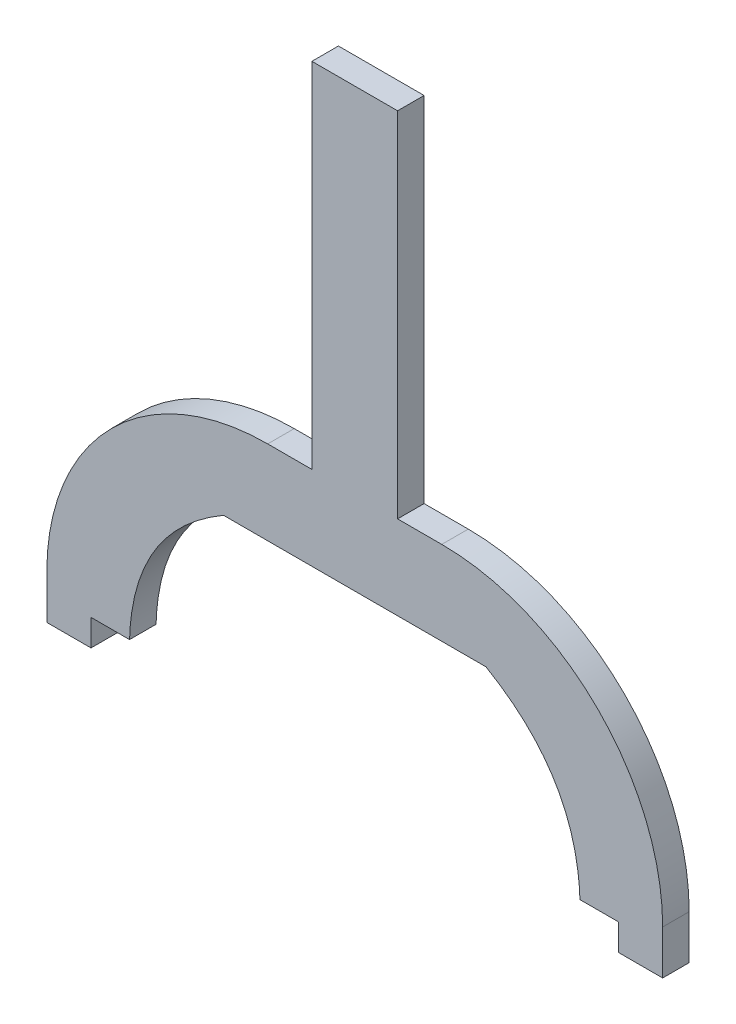
SolidWorks part; units mm, degrees
ref_plane "Front Plane" through (0, 0, 0) normal (0, 0, 1) x (1, 0, 0)
ref_plane "Top Plane" through (0, 0, 0) normal (0, 1, 0) x (1, 0, 0)
ref_plane "Right Plane" through (0, 0, 0) normal (1, 0, 0) x (0, 0, -1)
sketch "Sketch2" plane through (0, 0, 0) normal (0, 0, 1) x (1, 0, 0)
  line L40 (12.3158, -50.8) -> (88.5158, -50.8)
  line L41 (-12.3158, -50.8) -> (12.3158, -50.8) construction
  line L42 (-12.3158, -50.8) -> (-12.3158, 50.8)
  line L43 (-12.3158, 50.8) -> (12.3158, 50.8)
  line L44 (12.3158, -50.8) -> (12.3158, 50.8)
  line L45 (-12.3158, -50.8) -> (12.3158, 50.8) construction
  line L46 (-12.3158, 50.8) -> (12.3158, -50.8) construction
  line L47 (88.5158, -50.8) -> (88.5158, -127)
  line L53 (37.7158, -119.38) -> (37.7158, -74.93)
  line L54 (37.7158, -74.93) -> (-37.7158, -74.93)
  line L55 (-37.7158, -74.93) -> (-37.7158, -119.38)
  line L61 (-88.5158, -127) -> (-88.5158, -50.8)
  line L62 (-88.5158, -50.8) -> (-12.3158, -50.8)
  line L63 (37.7158, -119.38) -> (75.8158, -119.38)
  line L64 (75.8158, -119.38) -> (75.8158, -127)
  line L65 (75.8158, -127) -> (88.5158, -127)
  line L66 (-88.5158, -127) -> (-75.8158, -127)
  line L67 (-75.8158, -127) -> (-75.8158, -119.38)
  line L68 (-75.8158, -119.38) -> (-37.7158, -119.38)
  point P0 (0, 0)
  dimension "D1" = 76.2
  dimension "D2" = 44.45
  dimension "D3" = 101.6
  dimension "D4" = 7.62
  dimension "D5" = 38.1
  dimension "D6" = 12.7
  dimension "D7" = 76.2
extrude "Boss-Extrude1" add sketch "Sketch2" along normal blind 7.62
fillet "Fillet1" radius 63.5 2 edges at (88.5158, -50.8, 3.81) (-88.5158, -50.8, 3.81)
sketch "Sketch3" plane through (0, 0, 7.62) normal (0, 0, 1) x (1, 0, 0)
  line L0 (-75.8158, -119.38) -> (-64.7356, -119.38) construction
  line L1 (-75.8158, -119.38) -> (-37.7158, -119.38) construction
  line L2 (-37.7158, -74.93) -> (-37.7158, -119.38)
  line L3 (-37.7158, -119.38) -> (-64.7356, -119.38)
  spline S0 degree 2 poles (-64.7356, -119.38) (-63.8442, -90.0733) (-37.7158, -74.93) knots 0 0 0 1 1 1
extrude "Cut-Extrude1" cut sketch "Sketch3" against normal through all
ref_axis "Axis1" through (0, -74.93, 7.62) along (0, 0, -1)
ref_plane "Plane3" through (0, 0, 0) normal (-1, 0, 0) x (0, 0, -1)
mirror "Mirror1" about plane through (0, 0, 0) normal (-1, 0, 0) of "Cut-Extrude1"
equation "\"Foamcore\" = .1in"
equation "\"MDF\" = .3in"
equation "\"Gmaterial\"= \"MDF\""
equation "\"PVC-ID\" = \"1.590in\""
equation "\"PVC-OD\" = \"1.900in\""
equation "\"PVC-Sleeve-Width\" = \".51in\""
equation "\"D1@Boss-Extrude1\"=\"Gmaterial\""
equation "\"D4@Sketch2\"=\"Gmaterial\""
